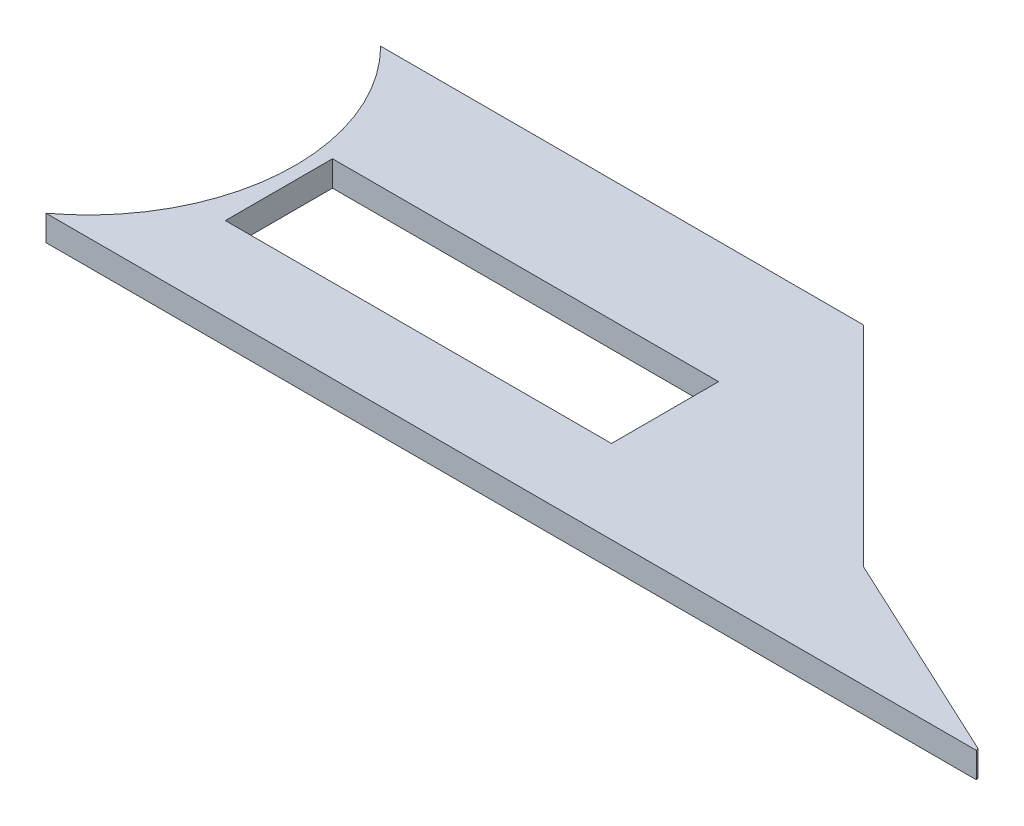
SolidWorks part; units mm, degrees
ref_plane "Спереди" through (0, 0, 0) normal (0, 0, 1) x (1, 0, 0)
ref_plane "Сверху" through (0, 0, 0) normal (0, 1, 0) x (1, 0, 0)
ref_plane "Справа" through (0, 0, 0) normal (1, 0, 0) x (0, 0, -1)
sketch "Эскиз1" plane through (0, 0, 0) normal (0, 1, 0) x (1, 0, 0)
  line L3 (-19.1171, -17.2996) -> (-49.3913, -17.2996)
  line L13 (-56.9238, -23.832) -> (16.3829, -23.832)
  line L14 (16.3829, -23.832) -> (-0.8369, -15.8022)
  line L15 (-0.8369, -15.8022) -> (-17.272, 0.6328)
  line L18 (-27.3967, -8.8996) -> (-19.1171, -8.8996)
  line L19 (-19.1171, -8.8996) -> (-19.1171, -17.2996)
  line L20 (-50.6164, -20.5658) -> (-44.084, -20.5658) construction
  line L23 (-27.3967, -8.8996) -> (-49.3913, -8.8996)
  line L25 (-44.084, -23.832) -> (-44.084, -17.2996) construction
  line L26 (-49.3913, -8.8996) -> (-49.3913, -17.2996)
  line L28 (-55.1464, 0.6328) -> (-17.272, 0.6328)
  arc A1 (-51.7409, -17.2996) -> (-55.1464, 0.6328) centre (-66.6008, -10.832) ccw
  arc A2 (-56.9238, -23.832) -> (-51.7409, -17.2996) centre (-66.6008, -10.832) ccw
  dimension "D3" = 6.5324
extrude "Бобышка-Вытянуть1" add sketch "Эскиз1" along normal blind 2
sketch "Эскиз2" plane through (0, 2, 0) normal (0, 1, 0) x (1, 0, 0)
  line L0 (16.3829, -23.832) -> (15.9601, -23.6348)
  line L1 (16.3829, -23.832) -> (-0.8369, -15.8022) construction
  line L2 (15.5753, -22.5775) -> (16.059, -23.9065) construction
  line L3 (15.9601, -23.6348) -> (16.059, -23.9065)
  line L4 (16.059, -23.9065) -> (-0.2545, -16.2993) construction
  line L5 (16.059, -23.9065) -> (16.3829, -23.832)
extrude "Вырез-Вытянуть1" cut sketch "Эскиз2" against normal through all and the other way blind 106.5
